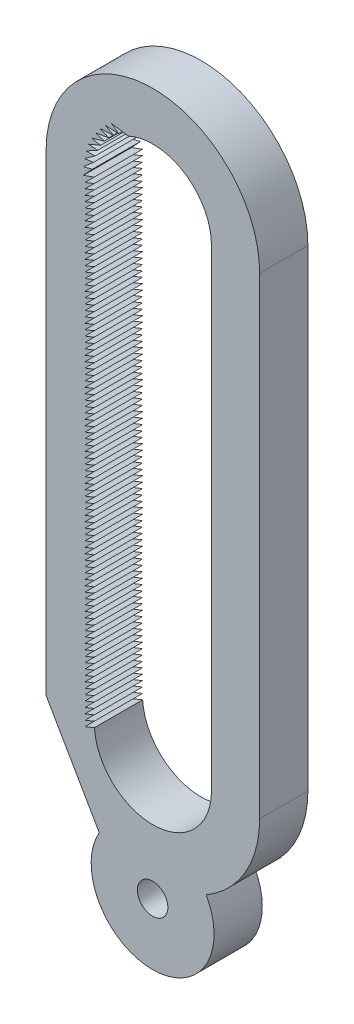
SolidWorks part; units mm, degrees
ref_plane "Piano frontale" through (0, 0, 0) normal (0, 0, 1) x (1, 0, 0)
ref_plane "Piano superiore" through (0, 0, 0) normal (0, 1, 0) x (1, 0, 0)
ref_plane "Piano destro" through (0, 0, 0) normal (1, 0, 0) x (0, 0, -1)
sketch "Schizzo1" plane through (0, 0, 0) normal (0, 0, 1) x (1, 0, 0)
  line L0 (0, -48.9995) -> (0, 48.9995) construction
  line L1 (-12.1501, -48.9995) -> (-12.1501, 48.9995)
  line L2 (12.1501, -48.9995) -> (12.1501, 48.9995)
  arc A0 (-12.1501, -48.9995) -> (12.1501, -48.9995) centre (0, -48.9995) ccw
  arc A1 (12.1501, 48.9995) -> (-12.1501, 48.9995) centre (0, 48.9995) ccw
  point P2 (0, 0)
extrude "Estrusione-Sottile1" add sketch "Schizzo1" along normal blind 10 thin thin type one direction wall 10
sketch "Schizzo2" plane through (0, 0, 10) normal (0, 0, 1) x (1, 0, 0)
  line L0 (-22.1501, -48.9995) -> (-11.1127, -68.1602)
  line L1 (-22.1501, -48.9995) -> (-24.8758, -48.9995)
  line L2 (-24.8758, -48.9995) -> (-24.8758, -68.1602)
  line L3 (-24.8758, -68.1602) -> (-11.1127, -68.1602)
  arc A0 (-22.1501, -48.9995) -> (22.1501, -48.9995) centre (0, -48.9995) ccw construction
extrude "Taglio-Estrusione2" cut sketch "Schizzo2" against normal blind 10
sketch "Schizzo3" plane through (0, 0, 10) normal (0, 0, 1) x (1, 0, 0)
  circle A1 centre (-0.0586, -74.4471) radius 12.75
  circle A2 centre (-0.0586, -74.4471) radius 3.1616
  point P3 (-0.0586, -74.4471)
extrude "Estrusione-Estrusione1" add sketch "Schizzo3" against normal blind 10
sketch "Schizzo4" plane through (0, 0, 10) normal (0, 0, 1) x (1, 0, 0)
  line L0 (-3.4838, 59.7909) -> (-8.6353, 60.5707)
  line L1 (-8.6353, 60.5707) -> (-3.8896, 57.1105)
  line L2 (-3.8896, 57.1105) -> (-3.4838, 59.7909)
  dimension "D1" = 5.8732
  dimension "D2" = 5.1514
  dimension "D3" = 2.6804
extrude "Taglio-Estrusione3" cut sketch "Schizzo4" against normal through all
pattern_circular "RipetizioneCircolare1" count 10 over 56 about axis through (0, 48.9995, 10) along (0, 0, -1) of "Taglio-Estrusione3" reverse direction yes
sketch "Schizzo5" plane through (0, 0, 10) normal (0, 0, 1) x (1, 0, 0)
  line L0 (-12.1493, 49.1338) -> (-14.0868, 47.1963)
  line L1 (-14.0868, 47.1963) -> (-11.8426, 48.1018)
  line L2 (-11.8426, 48.1018) -> (-12.1493, 49.1338)
  dimension "D1" = 2.42
  dimension "D2" = 2.74
  dimension "D3" = 1.0766
extrude "Taglio-Estrusione4" cut sketch "Schizzo5" against normal through all
sketch "Schizzo8" plane through (0, 0, 10) normal (0, 0, 1) x (1, 0, 0)
  line L0 (0, 71.1496) -> (0, -61.1496) construction
  arc A1 (22.1501, 48.9995) -> (-22.1501, 48.9995) centre (0, 48.9995) ccw construction
  arc A2 (-12.1501, -48.9995) -> (12.1501, -48.9995) centre (0, -48.9995) ccw construction
pattern_linear "Ripetizione a L1" count 86 spacing 1.15 along (0, -1, 0) of "Taglio-Estrusione4"
equation "\"80ù\"=90"
